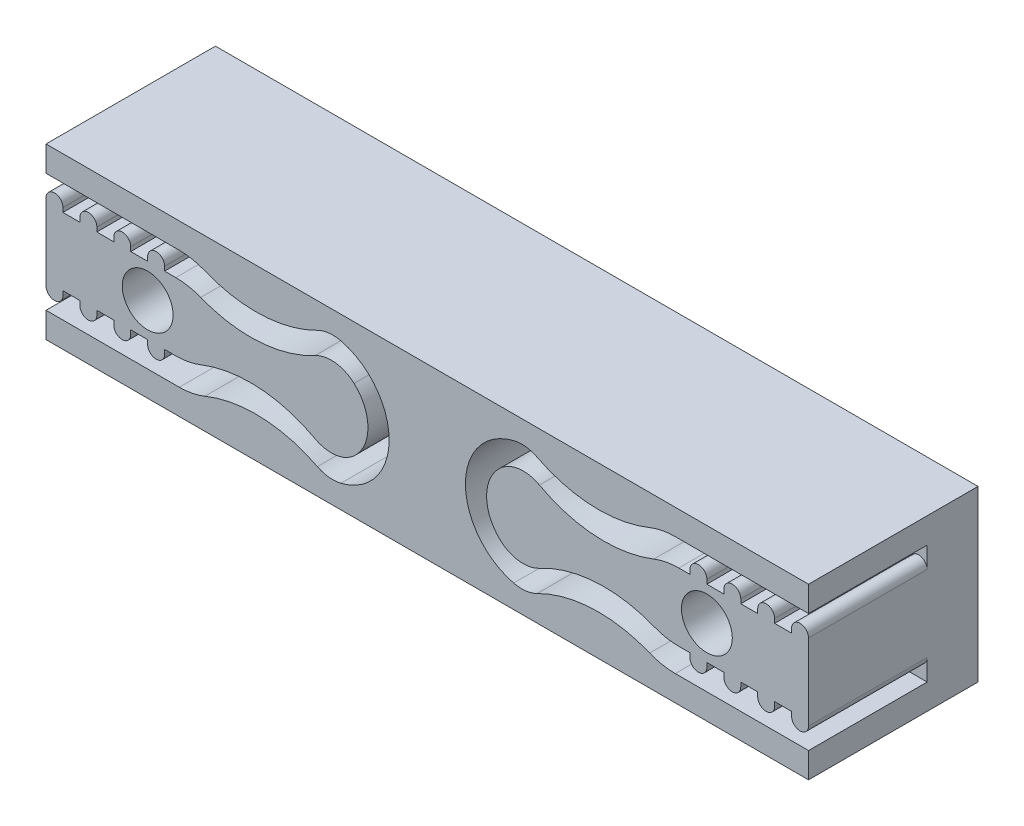
SolidWorks part; units mm, degrees
ref_plane "Спереди" through (0, 0, 0) normal (0, 0, 1) x (1, 0, 0)
ref_plane "Сверху" through (0, 0, 0) normal (0, 1, 0) x (1, 0, 0)
ref_plane "Справа" through (0, 0, 0) normal (1, 0, 0) x (0, 0, -1)
sketch "Эскиз1" plane through (0, 0, 0) normal (0, 0, 1) x (1, 0, 0)
  line L1 (-22.5, 4) -> (22.5, 4)
  line L2 (-22.5, 4) -> (-22.5, -4)
  line L3 (-22.5, -4) -> (22.5, -4)
  line L4 (22.5, 4) -> (22.5, -4)
  line L5 (-22.5, 4) -> (22.5, -4) construction
  line L6 (-22.5, -4) -> (22.5, 4) construction
  point P0 (0, 0)
  dimension "D1" = 8
  dimension "D2" = 45
extrude "Бобышка-Вытянуть1" add sketch "Эскиз1" along normal blind 10
sketch "Эскиз4" plane through (0, 4, 0) normal (0, 1, 0) x (1, 0, 0)
  line L1 (-22.5, 0) -> (22.5, 0)
  line L2 (-22.5, 0) -> (-22.5, -10)
  line L3 (-22.5, -10) -> (22.5, -10)
  line L4 (22.5, 0) -> (22.5, -10)
extrude "Бобышка-Вытянуть2" add sketch "Эскиз4" along normal blind 2
sketch "Эскиз5" plane through (0, 0, 10) normal (0, 0, 1) x (1, 0, 0)
  line L0 (-22.5, 1) -> (22.5, 1) construction
  line L1 (-22.5, 6) -> (-22.5, -4) construction
  line L2 (22.5, -4) -> (22.5, 6) construction
  line L3 (0, 6) -> (0, -4) construction
  line L4 (-22.5, 6) -> (22.5, 6) construction
  line L5 (-22.5, -4) -> (22.5, -4) construction
sketch "Эскиз6" plane through (0, 0, 10) normal (0, 0, 1) x (1, 0, 0)
  line L0 (0, 1) -> (-6, 1)
  line L1 (-22.5, 1) -> (22.5, 1) construction
  line L2 (0, 1) -> (-6, 1)
  line L3 (22.5, -2.5) -> (22.5, -1)
  line L4 (-22.5, 3) -> (-17, 3)
  line L5 (-22.5, 3) -> (-22.5, 4.5)
  line L6 (-22.5, 6) -> (-22.5, -4) construction
  line L7 (-22.5, -1) -> (-17, -1)
  line L8 (-17, 3) -> (-14.8421, 3)
  line L9 (-17, -1) -> (-14.8421, -1)
  line L10 (-22.5, 4.5) -> (-14.6336, 4.5)
  line L11 (-22.5, -2.5) -> (-14.6336, -2.5)
  line L12 (-17, 3) -> (-14.8421, 3)
  line L13 (0, 6) -> (0, -4)
  line L14 (-22.5, 3) -> (-22.5, 3.75)
  line L15 (-22.5, -2.5) -> (-22.5, -1)
  line L16 (22.5, 3) -> (22.5, 3.75)
  line L17 (17, 3) -> (14.8421, 3)
  line L18 (22.5, -2.5) -> (14.6336, -2.5)
  line L19 (22.5, 4.5) -> (14.6336, 4.5)
  line L20 (17, -1) -> (14.8421, -1)
  line L21 (17, 3) -> (14.8421, 3)
  line L22 (22.5, -1) -> (17, -1)
  line L23 (22.5, 3) -> (22.5, 4.5)
  line L24 (22.5, 3) -> (17, 3)
  arc A0 (6.6174, 3.1281) -> (4.3191, 2.8506) centre (5.6638, 1.3701) ccw
  arc A1 (-4.3191, -0.8506) -> (-4.3191, 2.8506) centre (-6, 1) ccw
  arc A2 (-5.0991, -2.6402) -> (-5.0991, 4.6402) centre (-6, 1) ccw
  arc A3 (-13.372, 2.7201) -> (-6.6174, 3.1281) centre (-10.4319, 10.1602) ccw
  arc A4 (-13.372, -0.7201) -> (-6.6174, -1.1281) centre (-10.4319, -8.1602) cw
  arc A5 (-13.1253, 4.2047) -> (-6.4854, 4.4818) centre (-10.1088, 11.6142) ccw
  arc A6 (-13.1253, -2.2047) -> (-6.4854, -2.4818) centre (-10.1088, -9.6142) cw
  arc A7 (-5.0991, 4.6402) -> (-6.4854, 4.4818) centre (-5.5796, 2.6987) ccw
  arc A8 (-6.6174, -1.1281) -> (-4.3191, -0.8506) centre (-5.6638, 0.6299) ccw
  arc A9 (-6.4854, -2.4818) -> (-5.0991, -2.6402) centre (-5.5796, -0.6987) ccw
  arc A10 (-14.6336, 4.5) -> (-13.1253, 4.2047) centre (-14.6336, 0.5) cw
  arc A11 (-14.8421, 3) -> (-13.372, 2.7201) centre (-14.8421, -1) cw
  arc A12 (-14.8421, -1) -> (-13.372, -0.7201) centre (-14.8421, 3) ccw
  arc A13 (-13.1253, -2.2047) -> (-14.6336, -2.5) centre (-14.6336, 1.5) cw
  arc A14 (-6.6174, 3.1281) -> (-4.3191, 2.8506) centre (-5.6638, 1.3701) cw
  arc A15 (13.1253, -2.2047) -> (14.6336, -2.5) centre (14.6336, 1.5) ccw
  arc A16 (14.8421, -1) -> (13.372, -0.7201) centre (14.8421, 3) cw
  arc A17 (14.8421, 3) -> (13.372, 2.7201) centre (14.8421, -1) ccw
  arc A18 (14.6336, 4.5) -> (13.1253, 4.2047) centre (14.6336, 0.5) ccw
  arc A19 (6.4854, -2.4818) -> (5.0991, -2.6402) centre (5.5796, -0.6987) cw
  arc A20 (6.6174, -1.1281) -> (4.3191, -0.8506) centre (5.6638, 0.6299) cw
  arc A21 (5.0991, 4.6402) -> (6.4854, 4.4818) centre (5.5796, 2.6987) cw
  arc A22 (13.1253, -2.2047) -> (6.4854, -2.4818) centre (10.1088, -9.6142) ccw
  arc A23 (13.1253, 4.2047) -> (6.4854, 4.4818) centre (10.1088, 11.6142) cw
  arc A24 (13.372, -0.7201) -> (6.6174, -1.1281) centre (10.4319, -8.1602) ccw
  arc A25 (13.372, 2.7201) -> (6.6174, 3.1281) centre (10.4319, 10.1602) cw
  arc A26 (5.0991, -2.6402) -> (5.0991, 4.6402) centre (6, 1) cw
  arc A27 (4.3191, -0.8506) -> (4.3191, 2.8506) centre (6, 1) cw
  point P30 (-6, 4.75)
  point P33 (-6, -1.5)
  point P36 (-6, -2.75)
  point P39 (-13.7677, 4.5)
  point P42 (-14, 3)
  point P45 (-14, -1)
  point P48 (-13.7677, -2.5)
  point P51 (-6, 3.5)
  point P87 (6, 3.5)
  point P88 (13.7677, -2.5)
  point P89 (14, -1)
  point P90 (14, 3)
  point P91 (13.7677, 4.5)
  point P92 (6, -2.75)
  point P93 (6, -1.5)
  point P94 (6, 4.75)
  line M10 (22.5, -4) -> (22.5, 6)
  line M12 (-22.5, 6) -> (-22.5, -4)
  dimension "D3" = 5
  dimension "D4" = 7.5
  dimension "D8" = 1.5
  dimension "D9" = 2
  dimension "D10" = 2
  dimension "D11" = 2
  dimension "D12" = 4
  dimension "D13" = 2
  dimension "D5" = 6
  dimension "D7" = 3
extrude "Вырез-Вытянуть1" cut sketch "Эскиз6" against normal blind 7 contours A3 A14 A1 L2 A2 A7 A5 A10 L10 L5 L4 L8 A11 M12 | A13 A6 A9 A2 L2 A1 A8 A4 A12 L9 L7 L11 M12 | A20 A27 A0 A25 A17 L17 L24 L19 A18 A23 A21 A26 A19 A22 A15 L18 L22 L20 A16 A24 M10 region at (-12.2866, -1.4019, 10) region at (-12.2866, 3.4019, 10) region at (18.5668, -2.2844, 10)
sketch "Эскиз7" plane through (0, 0, 10) normal (0, 0, 1) x (1, 0, 0)
  line L0 (-22.5, 3) -> (-22.5, 3.75)
  line L1 (-22.5, 4.5) -> (-22.5, 3) construction
  line L2 (-22.5, 3.75) -> (-21.5, 3.75)
  line L3 (-21.5, 3.75) -> (-21.5, 3)
  line L4 (-22.5, 3) -> (-14.8421, 3) construction
  line L5 (-22.5, 3) -> (-21.5, 3)
  line L6 (-20.5, 3) -> (-20.5, 3.75)
  line L7 (-20.5, 3.75) -> (-19.5, 3.75)
  line L8 (-19.5, 3.75) -> (-19.5, 3)
  line L9 (-20.5, 3) -> (-19.5, 3)
  line L10 (-18.5, 3) -> (-18.5, 3.75)
  line L11 (-18.5, 3.75) -> (-17.5, 3.75)
  line L12 (-17.5, 3.75) -> (-17.5, 3)
  line L13 (-18.5, 3) -> (-17.5, 3)
  line L14 (-16.5, 3) -> (-16.5, 3.75)
  line L15 (-16.5, 3.75) -> (-15.5, 3.75)
  line L16 (-15.5, 3.75) -> (-15.5, 3)
  line L17 (-16.5, 3) -> (-15.5, 3)
  line L18 (-20.5, -1.75) -> (-20.5, -1)
  line L19 (-20.5, -1) -> (-19.5, -1)
  line L20 (-19.5, -1) -> (-19.5, -1.75)
  line L21 (-20.5, -1.75) -> (-19.5, -1.75)
  line L22 (-18.5, -1.75) -> (-18.5, -1)
  line L23 (-18.5, -1) -> (-17.5, -1)
  line L24 (-17.5, -1) -> (-17.5, -1.75)
  line L25 (-18.5, -1.75) -> (-17.5, -1.75)
  line L26 (-16.5, -1.75) -> (-16.5, -1)
  line L27 (-16.5, -1) -> (-15.5, -1)
  line L28 (-15.5, -1) -> (-15.5, -1.75)
  line L29 (-16.5, -1.75) -> (-15.5, -1.75)
  line L30 (-22.5, -1.75) -> (-22.5, -1)
  line L31 (-22.5, -1) -> (-21.5, -1)
  line L32 (-21.5, -1) -> (-21.5, -1.75)
  line L33 (-22.5, -1.75) -> (-21.5, -1.75)
  line L34 (0, 6) -> (0, -4)
  line L35 (-22.5, 6) -> (22.5, 6) construction
  line L36 (22.5, -1.75) -> (21.5, -1.75)
  line L37 (21.5, -1) -> (21.5, -1.75)
  line L38 (22.5, -1) -> (21.5, -1)
  line L39 (22.5, -1.75) -> (22.5, -1)
  line L40 (16.5, -1.75) -> (15.5, -1.75)
  line L41 (15.5, -1) -> (15.5, -1.75)
  line L42 (16.5, -1) -> (15.5, -1)
  line L43 (16.5, -1.75) -> (16.5, -1)
  line L44 (18.5, -1.75) -> (17.5, -1.75)
  line L45 (17.5, -1) -> (17.5, -1.75)
  line L46 (18.5, -1) -> (17.5, -1)
  line L47 (18.5, -1.75) -> (18.5, -1)
  line L48 (20.5, -1.75) -> (19.5, -1.75)
  line L49 (19.5, -1) -> (19.5, -1.75)
  line L50 (20.5, -1) -> (19.5, -1)
  line L51 (20.5, -1.75) -> (20.5, -1)
  line L52 (16.5, 3) -> (15.5, 3)
  line L53 (15.5, 3.75) -> (15.5, 3)
  line L54 (16.5, 3.75) -> (15.5, 3.75)
  line L55 (16.5, 3) -> (16.5, 3.75)
  line L56 (18.5, 3) -> (17.5, 3)
  line L57 (17.5, 3.75) -> (17.5, 3)
  line L58 (18.5, 3.75) -> (17.5, 3.75)
  line L59 (18.5, 3) -> (18.5, 3.75)
  line L60 (20.5, 3) -> (19.5, 3)
  line L61 (19.5, 3.75) -> (19.5, 3)
  line L62 (20.5, 3.75) -> (19.5, 3.75)
  line L63 (20.5, 3) -> (20.5, 3.75)
  line L64 (22.5, 3) -> (21.5, 3)
  line L65 (21.5, 3.75) -> (21.5, 3)
  line L66 (22.5, 3.75) -> (21.5, 3.75)
  line L67 (22.5, 3) -> (22.5, 3.75)
  line M4 (-14.8421, 3) -> (-22.5, 3)
  line M6 (-22.5, -1) -> (-14.8421, -1)
  dimension "D1" = 0.75
  dimension "D2" = 1
  dimension "D3" = 4
  dimension "D4" = 2
extrude "Бобышка-Вытянуть3" add sketch "Эскиз7" against normal blind 7 contours L3 L2 L0 M4 | L8 L7 L6 M4 | L12 L11 L10 M4 | L16 L15 L14 M4 | L30 L33 L32 M6 | L18 L21 L20 M6 | L22 L25 L24 M6 | L26 L29 L28 M6 | L52 L55 L54 L53 | L56 L59 L58 L57 | L64 L67 L66 L65 | L36 L39 L38 L37 | L48 L51 L50 L49 | L44 L47 L46 L45 | L40 L43 L42 L41 | L60 L61 L62 L63 region at (-16, 3.375, 10) region at (-18, 3.375, 10) region at (-20, 3.375, 10) region at (-22, 3.375, 10) region at (-22, -1.375, 10) region at (-16, -1.375, 10) region at (-18, -1.375, 10) region at (-20, -1.375, 10) region at (22, -1.375, 10) region at (16, -1.375, 10) region at (18, -1.375, 10) region at (20, -1.375, 10) region at (16, 3.375, 10) region at (18, 3.375, 10) region at (22, 3.375, 10)
fillet "Скругление2" 2 edges at (-20.5, 3.75, 6.5) (-19.5, 3.75, 6.5) type full round first side face at (-20.5, 3.375, 6.5) second side face at (-19.5, 3.375, 6.5) middle face at (-20, 3.75, 6.5)
fillet "Скругление3" 2 edges at (-18.5, 3.75, 6.5) (-17.5, 3.75, 6.5) type full round first side face at (-18.5, 3.375, 6.5) second side face at (-17.5, 3.375, 6.5) middle face at (-18, 3.75, 6.5)
fillet "Скругление4" 2 edges at (-16.5, 3.75, 6.5) (-15.5, 3.75, 6.5) type full round first side face at (-16.5, 3.375, 6.5) second side face at (-15.5, 3.375, 6.5) middle face at (-16, 3.75, 6.5)
fillet "Скругление5" 2 edges at (-22.5, 3.75, 6.5) (-21.5, 3.75, 6.5) type full round first side face at (-22.5, 1, 6) second side face at (-21.5, 3.375, 6.5) middle face at (-22, 3.75, 6.5)
fillet "Скругление7" 2 edges at (-22.5, -1.75, 6.5) (-21.5, -1.75, 6.5) type full round first side face at (-22.5, 0.9167, 6) second side face at (-21.5, -1.375, 6.5) middle face at (-22, -1.75, 6.5)
fillet "Скругление8" 2 edges at (-20.5, -1.75, 6.5) (-19.5, -1.75, 6.5) type full round first side face at (-20.5, -1.375, 6.5) second side face at (-19.5, -1.375, 6.5) middle face at (-20, -1.75, 6.5)
fillet "Скругление9" 2 edges at (-18.5, -1.75, 6.5) (-17.5, -1.75, 6.5) type full round first side face at (-18.5, -1.375, 6.5) second side face at (-17.5, -1.375, 6.5) middle face at (-18, -1.75, 6.5)
fillet "Скругление10" 2 edges at (-16.5, -1.75, 6.5) (-15.5, -1.75, 6.5) type full round first side face at (-16.5, -1.375, 6.5) second side face at (-15.5, -1.375, 6.5) middle face at (-16, -1.75, 6.5)
fillet "Скругление11" 2 edges at (22.5, -1.75, 6.5) (21.5, -1.75, 6.5) type full round first side face at (22.5, 1, 6) second side face at (21.5, -1.375, 6.5) middle face at (22, -1.75, 6.5)
fillet "Скругление12" 2 edges at (20.5, -1.75, 6.5) (19.5, -1.75, 6.5) type full round first side face at (20.5, -1.375, 6.5) second side face at (19.5, -1.375, 6.5) middle face at (20, -1.75, 6.5)
fillet "Скругление13" 2 edges at (18.5, -1.75, 6.5) (17.5, -1.75, 6.5) type full round first side face at (18.5, -1.375, 6.5) second side face at (17.5, -1.375, 6.5) middle face at (18, -1.75, 6.5)
fillet "Скругление14" 2 edges at (16.5, -1.75, 6.5) (15.5, -1.75, 6.5) type full round first side face at (16.5, -1.375, 6.5) second side face at (15.5, -1.375, 6.5) middle face at (16, -1.75, 6.5)
fillet "Скругление15" 2 edges at (15.5, 3.75, 6.5) (16.5, 3.75, 6.5) type full round first side face at (15.5, 3.375, 6.5) second side face at (16.5, 3.375, 6.5) middle face at (16, 3.75, 6.5)
fillet "Скругление16" 2 edges at (18.5, 3.75, 6.5) (17.5, 3.75, 6.5) type full round first side face at (18.5, 3.375, 6.5) second side face at (17.5, 3.375, 6.5) middle face at (18, 3.75, 6.5)
fillet "Скругление17" 2 edges at (19.5, 3.75, 6.5) (20.5, 3.75, 6.5) type full round first side face at (19.5, 3.375, 6.5) second side face at (20.5, 3.375, 6.5) middle face at (20, 3.75, 6.5)
fillet "Скругление18" 2 edges at (22.5, 3.75, 6.5) (21.5, 3.75, 6.5) type full round first side face at (22.5, 1.0833, 6) second side face at (21.5, 3.375, 6.5) middle face at (22, 3.75, 6.5)
sketch "Эскиз8" plane through (0, 0, 10) normal (0, 0, 1) x (1, 0, 0)
  line L0 (-22.5, 1) -> (-10.5, 1)
  line L1 (-22.5, 1) -> (22.5, 1) construction
  line L2 (0, 6) -> (0, -4)
  line L3 (-22.5, -4) -> (22.5, -4) construction
  line L4 (-16.5, 1) -> (-22.5, 1)
  circle A0 centre (-16.5, 1) radius 1.5
  circle A3 centre (16.5, 1) radius 1.5
  dimension "D1" = 3
  dimension "D2" = 6
extrude "Вырез-Вытянуть3" cut sketch "Эскиз8" against normal through all contours L4 A0 L0 | A3 | A0 region at (-16.5, 0.3634, 10) region at (16.5, 1, 10)
